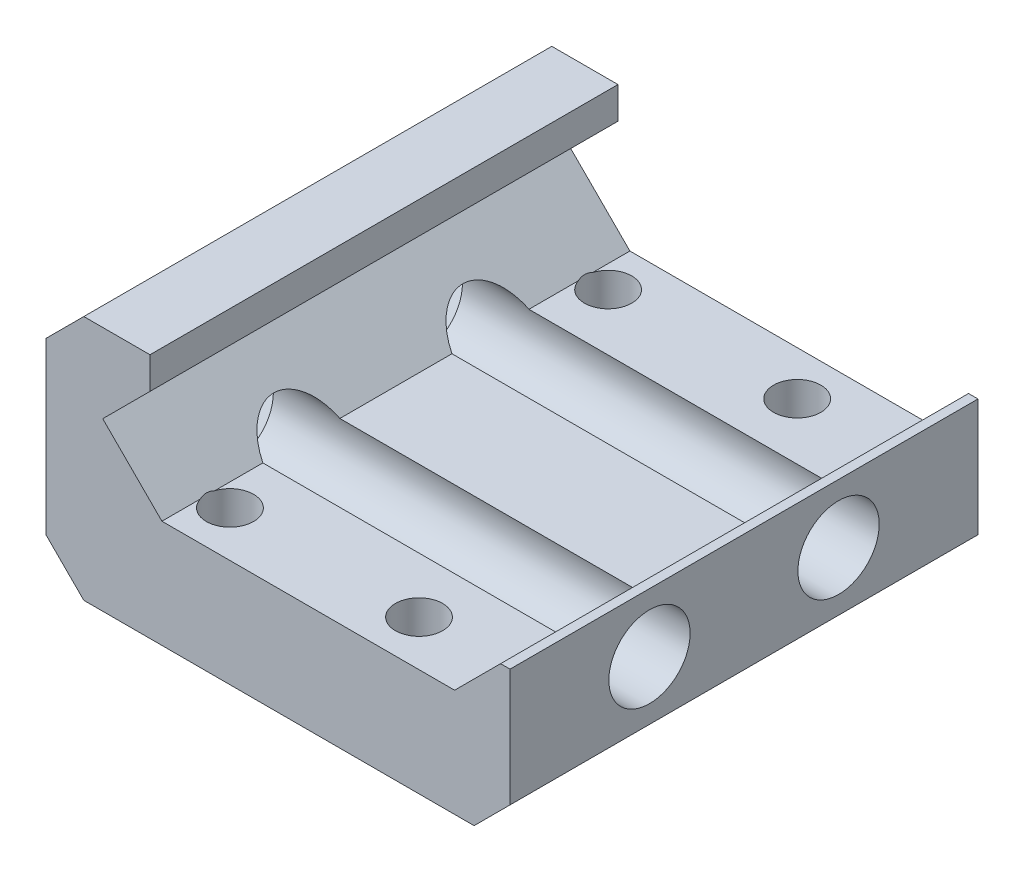
SolidWorks part; units mm, degrees
ref_plane "Płaszczyzna przednia" through (0, 0, 0) normal (0, 0, 1) x (1, 0, 0)
ref_plane "Płaszczyzna górna" through (0, 0, 0) normal (0, 1, 0) x (1, 0, 0)
ref_plane "Płaszczyzna prawa" through (0, 0, 0) normal (1, 0, 0) x (0, 0, -1)
sketch "Szkic1" plane through (0, 0, 0) normal (0, 0, 1) x (1, 0, 0)
  line L0 (-3, 4.18) -> (2.5, 4.18)
  line L2 (-3, -8.82) -> (-3, 4.18)
  line L5 (21.74, 0) -> (21.74, -7.02) construction
  line L6 (1.37, -1.37) -> (20.37, -1.37) construction
  line L7 (2.5, 4.18) -> (2.5, 2.5)
  line L8 (2.5, 2.5) -> (0, 0)
  line L9 (0, 0) -> (3.13, -3.13)
  line L10 (3.13, -3.13) -> (18.61, -3.13)
  line L11 (18.61, -3.13) -> (21.54, -0.2)
  line L14 (21.54, -0.2) -> (21.54, -6.92)
  line L17 (21.54, -6.92) -> (19.64, -8.82)
  line L18 (-3, -8.82) -> (19.64, -8.82)
  line L19 (1.37, -1.37) -> (1.37, 1.37) construction
  line L20 (1.37, 1.37) -> (20.37, 1.37) construction
  line L21 (20.37, -1.37) -> (20.37, 1.37) construction
  dimension "D1" = 45
  dimension "D2" = 45
  dimension "D3" = 5.5
  dimension "D4" = 1.68
  dimension "D5" = 13
  dimension "D6" = 0.3
  dimension "D7" = 19
  dimension "D8" = 2.74
  dimension "D9" = 4.5
  dimension "D10" = 3
  dimension "D11" = 0.2
extrude "Dodanie-wyciągnięcie3" add sketch "Szkic1" along normal blind 24.75
sketch "Szkic3" plane through (21.54, 0, 0) normal (1, 0, 0) x (0, 0, -1)
  line L0 (-24.75, -8.82) -> (0, -8.82) construction
  line L1 (-7.375, -3.82) -> (-17.375, -3.82) construction
  line L3 (-24.75, -6.92) -> (0, -6.92) construction
  line L4 (-24.75, -6.92) -> (0, -6.92) construction
  line L5 (-12.375, -6.92) -> (-12.375, -3.82) construction
  circle A0 centre (-17.375, -3.82) radius 2.15
  circle A1 centre (-7.375, -3.82) radius 2.15
  dimension "D1" = 10
  dimension "D2" = 4.3
  dimension "D3" = 5
  dimension "D4" = 5
extrude "Wytnij-wyciągnięcie1" cut sketch "Szkic3" against normal through all
sketch "Szkic4" plane through (0, -3.13, 0) normal (0, 1, 0) x (1, 0, 0)
  line L0 (18.61, -24.75) -> (3.13, -24.75) construction
  circle A0 centre (0, -2.75) radius 2
  circle A1 centre (0, -22) radius 2
  dimension "D2" = 2.75
  dimension "D3" = 2.75
extrude "Wytnij-wyciągnięcie2" [suppressed] cut sketch "Szkic4" against normal blind 6
sketch "Szkic7" [suppressed] plane through (0, -3.13, 0) normal (0, 1, 0) x (1, 0, 0)
  circle A0 centre (0, -2.75) radius 2.5
  circle A1 centre (0, -22) radius 2.5
  dimension "D1" = 2.75
  dimension "D2" = 19.25
extrude "Wytnij-wyciągnięcie3" [suppressed] cut sketch "Szkic7" against normal blind 1.5
sketch "Sketch1" plane through (0, 0, 24.75) normal (0, 0, 1) x (1, 0, 0)
  line L0 (21.04, -0.7) -> (21.54, -0.7)
  line L1 (21.54, -0.2) -> (18.61, -3.13) construction
  line L2 (21.54, -6.92) -> (21.54, -0.2) construction
  line L13 (-3, -8.82) -> (19.64, -8.82)
  line L14 (19.64, -8.82) -> (21.54, -6.92)
  line L15 (21.54, -6.92) -> (21.54, -0.2)
  line L16 (21.54, -0.2) -> (18.61, -3.13)
  line L17 (18.61, -3.13) -> (3.13, -3.13)
  line L18 (3.13, -3.13) -> (0, 0)
  line L19 (0, 0) -> (2.5, 2.5)
  line L20 (2.5, 2.5) -> (2.5, 4.18)
  line L21 (2.5, 4.18) -> (-3, 4.18)
  line L22 (-3, 4.18) -> (-3, -8.82)
  line L25 (21.54, -0.7) -> (21.54, -0.2)
  line L26 (21.54, -0.2) -> (21.04, -0.7)
  dimension "D1" = 0.5
  dimension "D2" = 0
extrude "Cut-Extrude1" cut sketch "Sketch1" against normal through all
sketch "Sketch3" plane through (21.54, 0, 0) normal (1, 0, 0) x (0, 0, -1)
  circle A0 centre (-17.375, -3.82) radius 2.65
  circle A1 centre (-7.375, -3.82) radius 2.65
  dimension "D1" = 5.3
chamfer "Chamfer1" distance 2 angle 45 2 edges at (-3, 4.18, 12.375) (-3, -8.82, 12.375)
hole_wizard "Ø2.5 (2.5) Diameter Hole1" positions "Sketch4" profile "Sketch5" hole size "Ø2.5" standard "DIN" end condition through all
sketch "Sketch4" plane through (0, -8.82, 0) normal (0, -1, 0) x (-1, 0, 0)
  line L0 (-9.32, -19.9336) -> (-9.32, -24.75) construction
  line L4 (-4.32, -22.3418) -> (-9.32, -22.3418) construction
  line L6 (-9.32, 0) -> (-9.32, -4.8164) construction
  line L10 (-9.32, -2.3418) -> (-4.32, -2.3418) construction
  line L14 (1, -24.75) -> (-19.64, -24.75) construction
  point P0 (-4.32, -2.3418)
  point P4 (-14.32, -2.3418)
  point P5 (-14.32, -22.3418)
  point P6 (-4.32, -22.3418)
  dimension "D3" = 10
  dimension "D4" = 20
  dimension "D5" = 5
  dimension "D1" = 2
  dimension "D2" = 2
sketch "Sketch5" plane through (4.32, -8.82, 2.3418) normal (1, 0, 0) x (0, 0, -1)
  line L0 (0, 0) -> (0, 13)
  line L1 (0, 13) -> (1.25, 13)
  line L2 (1.25, 13) -> (1.25, 0)
  line L5 (1.25, 0) -> (0, 0)
  line L11 (0, -6.35) -> (0, 107.95) construction
  dimension "Thru Hole Dia." = 2.5
  dimension "Thru Hole Depth" = 13
sketch "Sketch6" plane through (-3, 0, 0) normal (-1, 0, 0) x (0, 0, 1)
  line L1 (9.3091, -7.17) -> (11.2432, -3.82)
  line L2 (11.2432, -3.82) -> (9.3091, -0.47)
  line L3 (9.3091, -0.47) -> (5.4409, -0.47)
  line L4 (5.4409, -0.47) -> (3.5068, -3.82)
  line L5 (3.5068, -3.82) -> (5.4409, -7.17)
  line L6 (5.4409, -7.17) -> (9.3091, -7.17)
  line L7 (15.4409, -7.17) -> (19.3091, -7.17)
  line L8 (19.3091, -7.17) -> (21.2432, -3.82)
  line L9 (21.2432, -3.82) -> (19.3091, -0.47)
  line L10 (19.3091, -0.47) -> (15.4409, -0.47)
  line L11 (15.4409, -0.47) -> (13.5068, -3.82)
  line L12 (13.5068, -3.82) -> (15.4409, -7.17)
  circle A0 centre (7.375, -3.82) radius 3.35 construction
  circle A1 centre (17.375, -3.82) radius 3.35 construction
  dimension "D1" = 6.7
extrude "Cut-Extrude2" cut sketch "Sketch6" against normal blind 2.5
